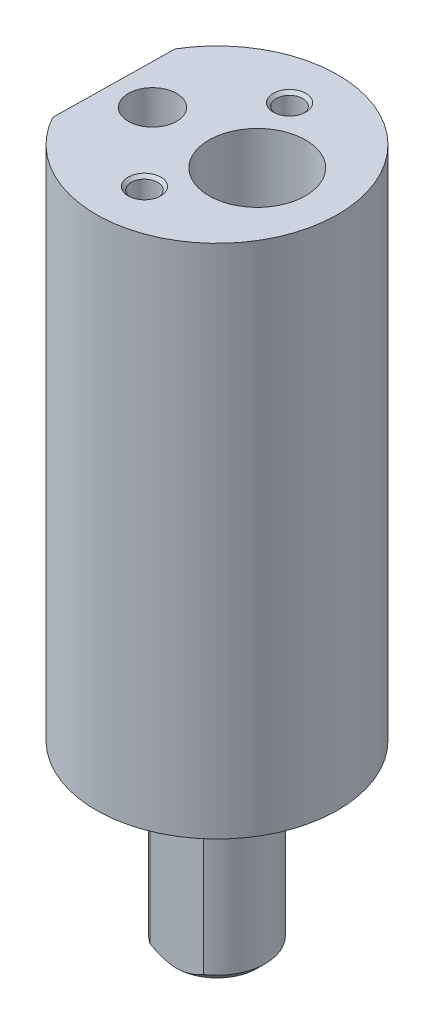
SolidWorks part; units mm, degrees
ref_plane "Front Plane" through (0, 0, 0) normal (0, 0, 1) x (1, 0, 0)
ref_plane "Top Plane" through (0, 0, 0) normal (0, 1, 0) x (1, 0, 0)
ref_plane "Right Plane" through (0, 0, 0) normal (1, 0, 0) x (0, 0, -1)
sketch "Sketch1" plane through (0, 0, 0) normal (0, 1, 0) x (1, 0, 0)
  line L0 (-3.3166, -5) -> (3.3166, -5)
  arc A0 (3.3166, -5) -> (-3.3166, -5) centre (0, 0) ccw
  dimension "D1" = 12
  dimension "D2" = 5
extrude "Boss-Extrude1" add sketch "Sketch1" along normal blind 22
sketch "Sketch2" plane through (0, 22, 0) normal (0, 1, 0) x (1, 0, 0)
  line L0 (-12.8761, 7.6946) -> (-13.1204, -7.2701)
  arc A0 (-13.1204, -7.2701) -> (-12.8761, 7.6946) centre (0, 0) ccw
  dimension "D1" = 30
  dimension "D2" = 13
extrude "Boss-Extrude2" add sketch "Sketch2" along normal blind 64
sketch "Sketch3" plane through (0, 86, 0) normal (0, 1, 0) x (1, 0, 0)
  line L0 (0, 0) -> (-24.8021, 0) construction
  circle A0 centre (-8, 0) radius 3
  dimension "D1" = 8
  dimension "D2" = 6
extrude "Cut-Extrude1" cut sketch "Sketch3" against normal blind 65
sketch "Sketch4" plane through (0, 86, 0) normal (0, 1, 0) x (1, 0, 0)
  circle A0 centre (5, 0) radius 6
  point P2 (0, 0)
  dimension "D1" = 12
  dimension "D2" = 5
extrude "Cut-Extrude2" cut sketch "Sketch4" against normal blind 52
hole_wizard "M4 Tapped Hole1" positions "Sketch5" profile "Sketch6" tap size "M4" standard "ISO"
sketch "Sketch5" plane through (0, 86, 0) normal (0, 1, 0) x (1, 0, 0)
  line L0 (0, 9) -> (0, -9) construction
  point P1 (0, 9)
  point P2 (0, -9)
  dimension "D1" = 9
  dimension "D2" = 9
sketch "Sketch6" plane through (0, 86, -9) normal (1, 0, 0) x (0, 0, 1)
  line L0 (0, 0) -> (0, 14.9914)
  line L1 (0, 14.9914) -> (1.65, 14)
  line L2 (1.65, 14) -> (1.65, 0.375)
  line L3 (1.65, 0.375) -> (2.025, 0)
  line L5 (2.025, 0) -> (0, 0)
  line L6 (-1.65, 0.375) -> (-2.025, 0) construction
  line L10 (0, 14.9914) -> (-1.65, 14) construction
  line L11 (0, -6.35) -> (0, 107.95) construction
  dimension "Tap Drill Dia." = 3.3
  dimension "Tap Drill Depth" = 14
  dimension "Near C'Sink Dia." = 4.05
  dimension "Near C'Sink Angle" = 90
  dimension "Drill Angle" = 118
cosmetic thread "Hole Thread1" parameters "D1"=8, "D2"=4
cosmetic thread "Hole Thread2" parameters "D1"=8, "D2"=4
sketch "Sketch7" plane through (-12.9983, 0, -0.2123) normal (-0.9999, 0, -0.0163) x (-0.0163, 0, 0.9999)
  line L0 (0, 22) -> (0, 86) construction
  line L1 (-7.4833, 22) -> (7.4833, 22) construction
  line L2 (-7.4833, 86) -> (7.4833, 86) construction
  circle A0 centre (0, 25) radius 1.5
  circle A1 centre (0, 54) radius 2.5
  point P10 (0, 0)
  point P11 (0, 0)
  dimension "D1" = 5
  dimension "D2" = 3
  dimension "D3" = 32
  dimension "D4" = 61
extrude "Cut-Extrude3" cut sketch "Sketch7" against normal blind 5
sketch "Sketch8" plane through (-12.9983, 0, -0.2123) normal (-0.9999, 0, -0.0163) x (-0.0163, 0, 0.9999)
  line L0 (0, 86) -> (0.1306, 22) construction
  line L1 (-7.4833, 86) -> (7.4833, 86) construction
  line L2 (-2.8694, 22) -> (3.1306, 22) construction
  circle A0 centre (0.0204, 76) radius 1
  circle A1 centre (0.1061, 34) radius 1
  dimension "D3" = 2
  dimension "D1" = 10
  dimension "D2" = 52
extrude "Cut-Extrude4" cut sketch "Sketch8" against normal blind 15
chamfer "Chamfer1" distance 1 angle 45 1 edges at (0, 0, -6)
